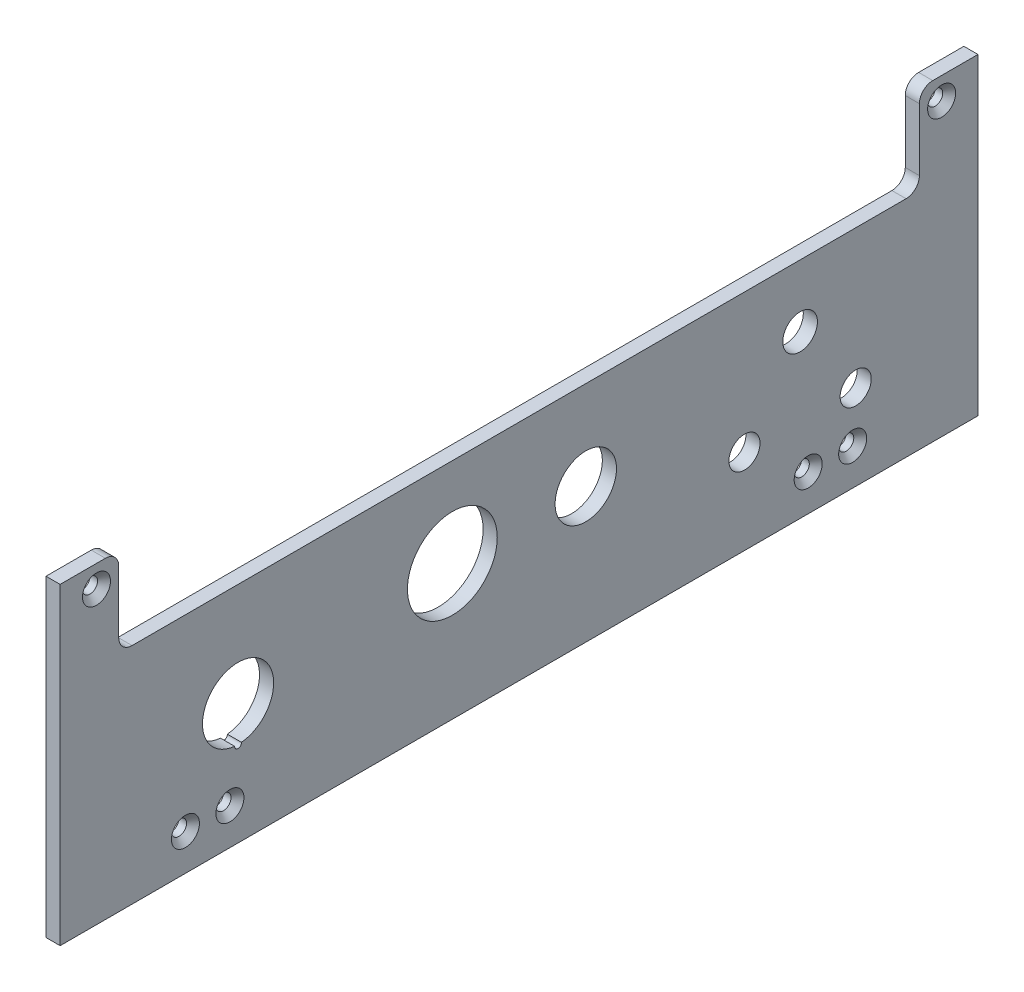
SolidWorks part; units mm, degrees
material "Garolite (G-10/FR4)"
ref_plane "Front Plane" through (0, 0, 0) normal (0, 0, 1) x (1, 0, 0)
ref_plane "Top Plane" through (0, 0, 0) normal (0, 1, 0) x (1, 0, 0)
ref_plane "Right Plane" through (0, 0, 0) normal (1, 0, 0) x (0, 0, -1)
sketch "Sketch1" plane through (0, 0, 0) normal (1, 0, 0) x (0, 0, -1)
  line L0 (103.175, 0) -> (103.175, 3.175)
  line L1 (-103.175, 0) -> (103.175, 0)
  line L2 (103.175, 3.175) -> (103.175, 47.175)
  line L3 (-103.175, 70.35) -> (-93, 70.35)
  line L4 (-103.175, 3.175) -> (-103.175, 47.175)
  line L5 (-103.175, 3.175) -> (-103.175, 0)
  line L6 (103.175, 47.175) -> (103.175, 50.35)
  line L7 (103.175, 50.35) -> (103.175, 70.35)
  line L8 (-90, 53.35) -> (-90, 67.35)
  line L9 (-103.175, 47.175) -> (-103.175, 50.35)
  line L10 (-103.175, 50.35) -> (-103.175, 70.35)
  line L11 (-87, 50.35) -> (87, 50.35)
  line L12 (0, 0) -> (0, 50.35) construction
  line L13 (103.175, 70.35) -> (93, 70.35)
  line L14 (90, 53.35) -> (90, 67.35)
  line L15 (103.175, 25.175) -> (-103.175, 25.175) construction
  arc A0 (-93, 70.35) -> (-90, 67.35) centre (-93, 67.35) cw
  arc A1 (-87, 50.35) -> (-90, 53.35) centre (-87, 53.35) cw
  arc A2 (87, 50.35) -> (90, 53.35) centre (87, 53.35) ccw
  arc A3 (93, 70.35) -> (90, 67.35) centre (93, 67.35) ccw
  dimension "D7" = 3
  dimension "D1" = 206.35
  dimension "D2" = 13.175
  dimension "D3" = 3.175
  dimension "D4" = 44
  dimension "D5" = 3.175
  dimension "D6" = 20
extrude "Boss-Extrude1" add sketch "Sketch1" along normal blind 3.175
hole_wizard "CSK for M3 Flat Head Machine Screw1" positions "Sketch3" profile "Sketch2" countersink size "M3" standard "Ansi Metric" end condition through all
sketch "Sketch3" plane through (3.175, 0, 0) normal (1, 0, 0) x (0, 0, -1)
  line L0 (-65, 8.175) -> (-103.175, 8.175) construction
  line L1 (-103.175, 70.35) -> (-103.175, 0) construction
  line L3 (-103.175, 0) -> (103.175, 0) construction
  line L13 (-103.175, 70.35) -> (-103.175, 0) construction
  line L14 (-93, 70.35) -> (-103.175, 70.35) construction
  point P0 (-75, 8.175)
  point P1 (-65, 8.175)
  point P83 (-95, 65.35)
  dimension "D1" = 8.175
  dimension "D2" = 28.175
  dimension "D3" = 10
  dimension "D4" = 8.175
  dimension "D5" = 5
sketch "Sketch2" plane through (3.175, 8.175, 75) normal (0, 1, 0) x (0, 0, -1)
  line L0 (0, 0) -> (0, 3.175)
  line L1 (0, 3.175) -> (1.7, 3.175)
  line L2 (1.7, 3.175) -> (1.7, 1.45)
  line L3 (1.7, 1.45) -> (3.15, 0)
  line L5 (3.15, 0) -> (0, 0)
  line L6 (-1.7, 1.45) -> (-3.15, 0) construction
  line L11 (0, -6.35) -> (0, 107.95) construction
  dimension "Thru Hole Dia." = 3.4
  dimension "Thru Hole Depth" = 3.175
  dimension "Near C'Sink Dia." = 6.3
  dimension "Near C'Sink Angle" = 90
mirror "Mirror1" about plane through (0, 0, 0) normal (0, 0, 1) of "CSK for M3 Flat Head Machine Screw1"
sketch "Sketch4" plane through (3.175, 0, 0) normal (1, 0, 0) x (0, 0, -1)
  line L0 (15, 30.35) -> (-15, 30.35) construction
  line L1 (-103.175, 70.35) -> (-103.175, 0) construction
  line L2 (0, 0) -> (0, 50.35) construction
  line L3 (87, 50.35) -> (-87, 50.35) construction
  line L4 (63.175, 19.175) -> (63.175, 36.35) construction
  line L5 (-63.175, 13.175) -> (15, 13.175) construction
  line L7 (-103.175, 0) -> (103.175, 0) construction
  line L8 (15, 13.175) -> (15, 30.35) construction
  line L9 (50.675, 19.175) -> (75.675, 19.175) construction
  line L10 (103.175, 0) -> (103.175, 70.35) construction
  arc A0 (-62.4009, 19.2125) -> (-63.9491, 19.2125) centre (-63.175, 27.175) ccw
  circle A1 centre (15, 30.35) radius 6.9
  circle A2 centre (63.175, 36.35) radius 3.9
  circle A3 centre (50.675, 19.175) radius 3.5
  circle A4 centre (75.675, 19.175) radius 3.5
  circle A5 centre (-15, 30.35) radius 10.1
  arc A6 (-63.9491, 19.2125) -> (-62.4009, 19.2125) centre (-63.175, 19.175) ccw
  dimension "D2" = 16
  dimension "D5" = 13.8
  dimension "D7" = 7.8
  dimension "D8" = 7
  dimension "D11" = 20.2
  dimension "D13" = 1.55
  dimension "D3" = 40
  dimension "D4" = 13.175
  dimension "D6" = 15
  dimension "D9" = 15
  dimension "D10" = 25
  dimension "D12" = 14
  dimension "D14" = 40
  dimension "D15" = 6
  dimension "D16" = 14
  dimension "D17" = 20
extrude "Cut-Extrude1" cut sketch "Sketch4" against normal through all
